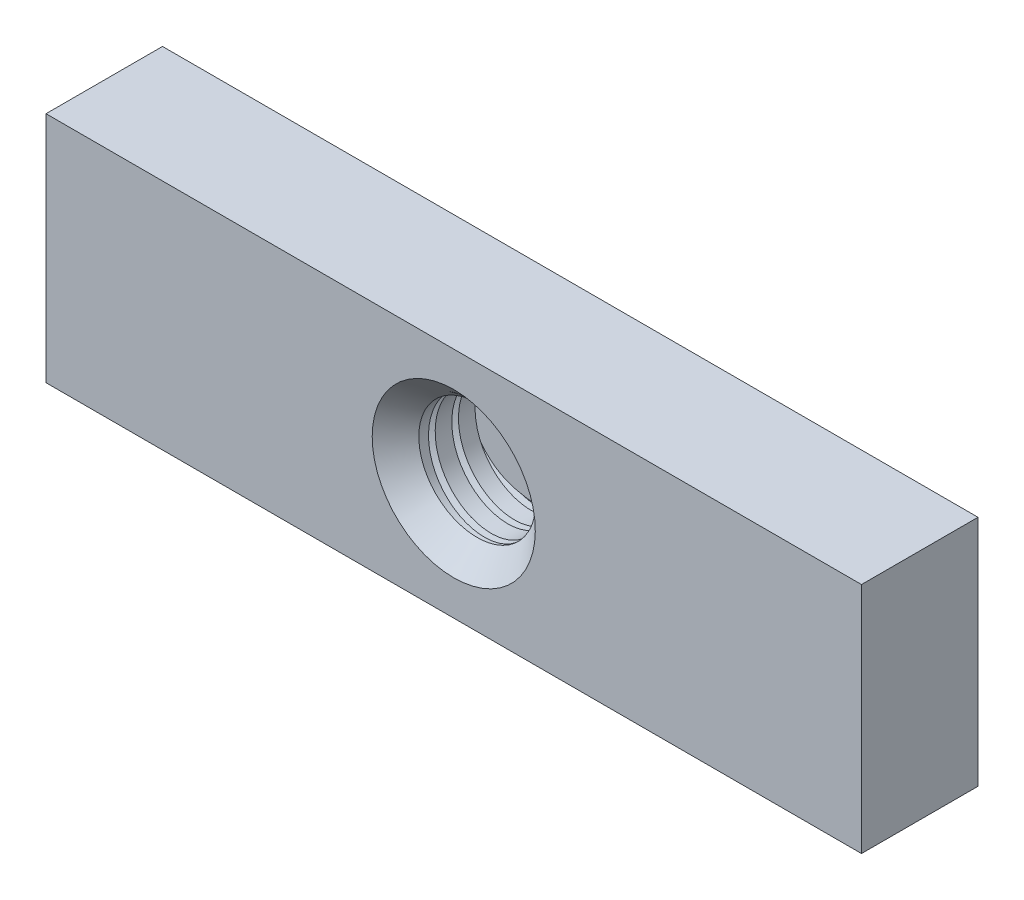
SolidWorks part; units mm, degrees
ref_plane "Front Plane" through (0, 0, 0) normal (0, 0, 1) x (1, 0, 0)
ref_plane "Top Plane" through (0, 0, 0) normal (0, 1, 0) x (1, 0, 0)
ref_plane "Right Plane" through (0, 0, 0) normal (1, 0, 0) x (0, 0, -1)
sketch "Sketch1" plane through (0, 0, 0) normal (0, 0, 1) x (1, 0, 0)
  line L0 (0, 10) -> (70, 10) construction
  line L1 (0, 0) -> (70, 0)
  line L2 (0, 0) -> (0, 20)
  line L3 (0, 20) -> (70, 20)
  line L4 (70, 0) -> (70, 20)
  line L5 (35, 20) -> (35, 0) construction
  circle A0 centre (35, 10) radius 5
  dimension "D3" = 10
  dimension "D1" = 20
  dimension "D2" = 70
extrude "Boss-Extrude1" add sketch "Sketch1" along normal blind 7
chamfer "Chamfer1" distance 2 angle 45 1 edges at (40, 10, 7)
sketch "Sketch2" plane through (0, 0, 7) normal (0, 0, 1) x (1, 0, 0)
  circle A0 centre (35, 10) radius 5 construction
  circle A1 centre (35, 10) radius 5 construction
  circle A2 centre (35, 10) radius 4
  dimension "D1" = 1
curve "Helix/Spiral1" pitch 2 height 14 radius 4 centre (35, 10, 7) axis (0, 0, -1) start towards (-1, 0, 0)
ref_plane "Plane1" through (31, 10, 7) normal (0, 0.9968, -0.0793) x (1, 0, 0)
sketch "Sketch3" plane through (31, 10, 7) normal (0, 0.9968, -0.0793) x (1, 0, 0)
  line L0 (0.0032, 0.2616) -> (-1.4968, 1.1277)
  line L1 (1.5032, 1.1277) -> (0.0032, 1.9937)
  line L2 (0.0032, 1.9937) -> (0.0032, 0.2616)
  line L3 (0.0032, 0.2616) -> (1.5032, 1.1277) construction
  line L4 (-1.4968, 1.1277) -> (0.0032, 1.9937)
  circle A0 centre (0.5032, 1.1277) radius 0.5 construction
  dimension "D1" = 1
sweep "Cut-Sweep2" cut profiles "Sketch3" path "Helix/Spiral1"
sketch "Sketch4" plane through (0, 0, 0) normal (0, 0, -1) x (-1, 0, 0)
  line L0 (0, 20) -> (0, 0)
  line L1 (0, 20) -> (-70, 20)
  line L2 (0, 0) -> (-70, 0)
  line L3 (-70, 20) -> (-70, 0)
extrude "Boss-Extrude2" add sketch "Sketch4" along normal blind 3
